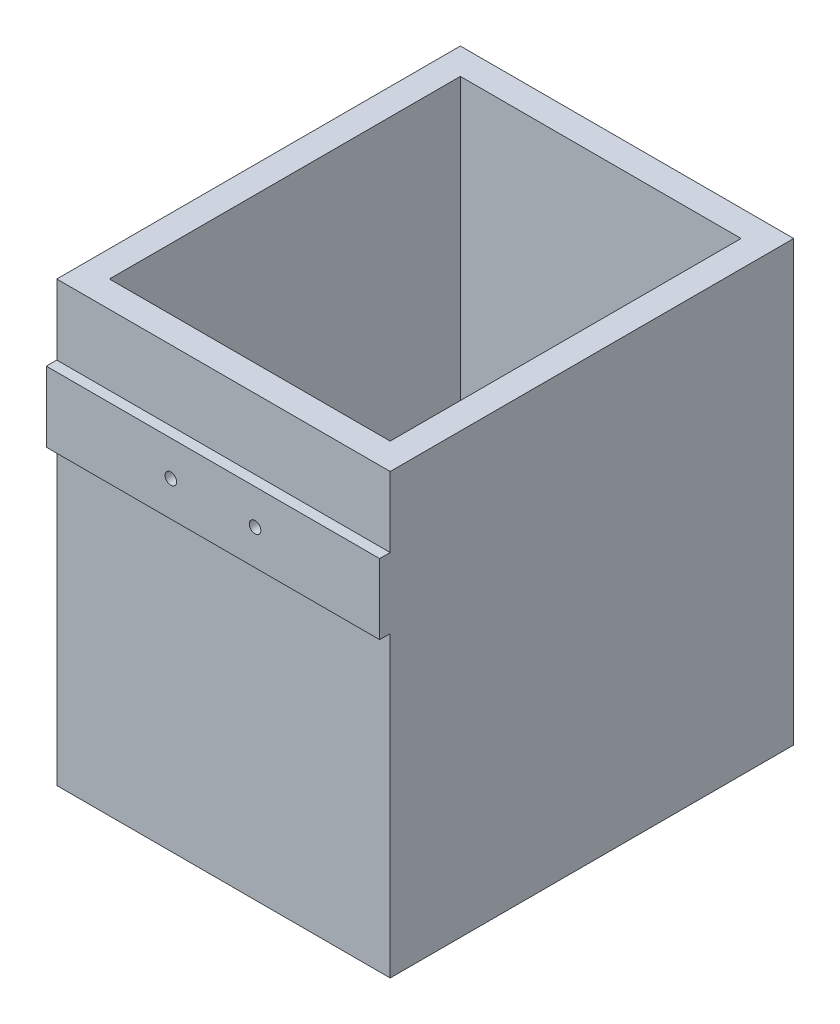
SolidWorks part; units mm, degrees
ref_plane "Front Plane" through (0, 0, 0) normal (0, 0, 1) x (1, 0, 0)
ref_plane "Top Plane" through (0, 0, 0) normal (0, 1, 0) x (1, 0, 0)
ref_plane "Right Plane" through (0, 0, 0) normal (1, 0, 0) x (0, 0, -1)
sketch "Sketch1" plane through (0, 0, 0) normal (0, 1, 0) x (1, 0, 0)
  line L1 (-40, -50) -> (40, -50)
  line L2 (-40, -50) -> (-40, 50)
  line L3 (-40, 50) -> (40, 50)
  line L4 (40, -50) -> (40, 50)
  line L5 (-40, -50) -> (40, 50) construction
  line L6 (-40, 50) -> (40, -50) construction
  point P0 (0, 0)
  dimension "D1" = 100
  dimension "D2" = 80
extrude "Boss-Extrude1" add sketch "Sketch1" along normal blind 9
sketch "Sketch2" plane through (0, 9, 0) normal (0, 1, 0) x (1, 0, 0)
  line L1 (-34, -42.7) -> (34, -42.7)
  line L2 (-34, -42.7) -> (-34, 42.7)
  line L3 (-34, 42.7) -> (34, 42.7)
  line L4 (34, -42.7) -> (34, 42.7)
  line L5 (-34, -42.7) -> (34, 42.7) construction
  line L6 (-34, 42.7) -> (34, -42.7) construction
  point P0 (0, 0)
  dimension "D1" = 85.4
  dimension "D2" = 68
extrude "Cut-Extrude1" cut sketch "Sketch2" against normal offset from surface (7 mm away) 2 contours L2 L1 L4 L3 up to face at (0, 0, 0)
sketch "Sketch3" plane through (0, 0, 0) normal (0, -1, 0) x (1, 0, 0)
  line L1 (-47.5, -57.5) -> (47.5, -57.5)
  line L2 (-47.5, -57.5) -> (-47.5, 57.5)
  line L3 (-47.5, 57.5) -> (47.5, 57.5)
  line L4 (47.5, -57.5) -> (47.5, 57.5)
  line L5 (-47.5, -57.5) -> (47.5, 57.5) construction
  line L6 (-47.5, 57.5) -> (47.5, -57.5) construction
  line L7 (-40, -50) -> (40, -50)
  line L8 (-40, -50) -> (-40, 50)
  line L9 (-40, 50) -> (40, 50)
  line L10 (40, -50) -> (40, 50)
  line L11 (-40, -50) -> (40, 50) construction
  line L12 (-40, 50) -> (40, -50) construction
  point P1 (0, 0)
  point P6 (0, 0)
  dimension "D1" = 115
  dimension "D2" = 95
extrude "Boss-Extrude2" add sketch "Sketch3" against normal blind 125
sketch "Sketch6" plane through (0, 0, 57.5) normal (0, 0, 1) x (1, 0, 0)
  line L0 (47.5, 125) -> (47.5, 0) construction
  line L1 (-47.5, 105) -> (47.5, 105)
  line L2 (-47.5, 105) -> (-47.5, 85)
  line L3 (-47.5, 85) -> (47.5, 85)
  line L4 (47.5, 105) -> (47.5, 85)
  line L5 (-47.5, 125) -> (-47.5, 0) construction
  line L6 (47.5, 125) -> (-47.5, 125) construction
  point P8 (-47.5, 88.2086)
  dimension "D1" = 20
  dimension "D2" = 20
extrude "Boss-Extrude4" add sketch "Sketch6" along normal blind 3
sketch "Sketch7" plane through (0, 0, 60.5) normal (0, 0, 1) x (1, 0, 0)
  line L0 (0, 0) -> (0, 125) construction
  line L1 (47.5, 125) -> (-47.5, 125) construction
  line L2 (-47.5, 95) -> (47.5, 95) construction
  line L3 (-47.5, 105) -> (-47.5, 85) construction
  line L4 (47.5, 85) -> (47.5, 105) construction
  circle A0 centre (-12, 95) radius 1.65
  circle A1 centre (12, 95) radius 1.65
  point P15 (10.35, 95)
  point P17 (-10.35, 95)
  dimension "D2" = 3.3
  dimension "D1" = 24
extrude "Cut-Extrude2" cut sketch "Sketch7" against normal up to surface (10.5 mm away) up to face at (0, 67, 50)
sketch "Sketch9" plane through (0, 0, 50) normal (0, 0, -1) x (-1, 0, 0)
  circle A0 centre (-12, 95) radius 3
  circle A1 centre (12, 95) radius 3
  circle A2 centre (-12, 95) radius 1.65 construction
  circle A3 centre (12, 95) radius 1.65 construction
  dimension "D1" = 6
extrude "Cut-Extrude3" cut sketch "Sketch9" against normal blind 3.2
